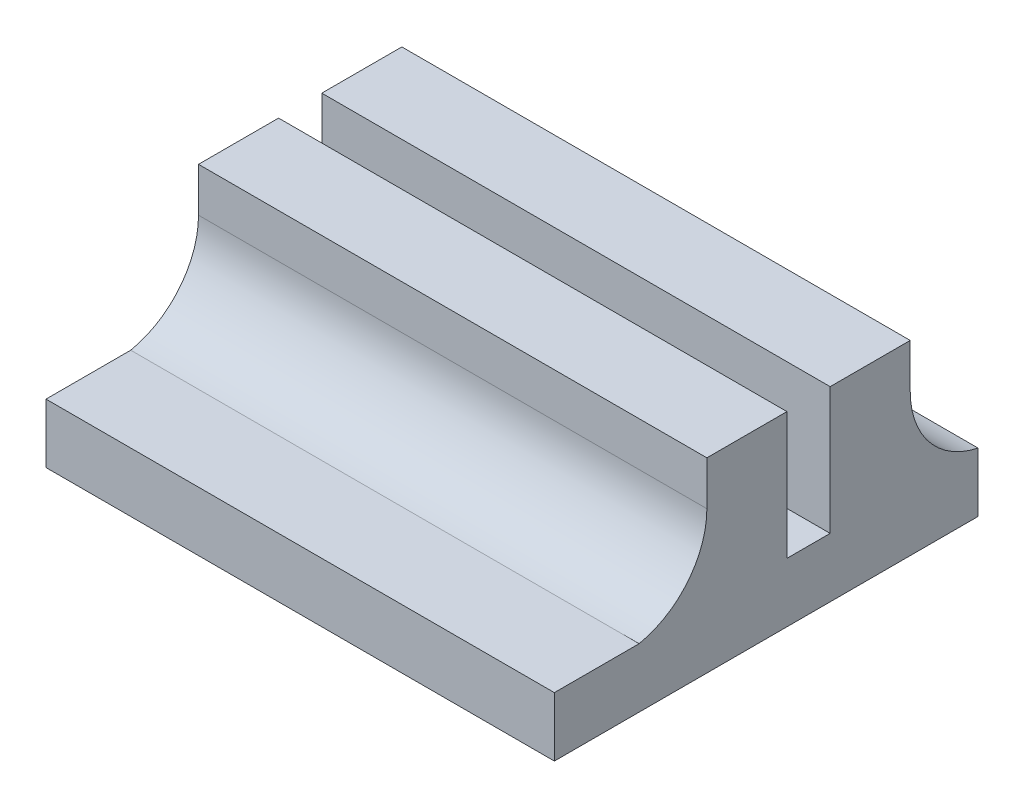
SolidWorks part; units mm, degrees
ref_plane "Front Plane" through (0, 0, 0) normal (0, 0, 1) x (1, 0, 0)
ref_plane "Top Plane" through (0, 0, 0) normal (0, 1, 0) x (1, 0, 0)
ref_plane "Right Plane" through (0, 0, 0) normal (1, 0, 0) x (0, 0, -1)
sketch "Sketch1" plane through (0, 0, 0) normal (0, 1, 0) x (1, 0, 0)
  line L1 (-30, 20) -> (30, 20)
  line L2 (-30, 20) -> (-30, -20)
  line L3 (-30, -20) -> (30, -20)
  line L4 (30, 20) -> (30, -20)
  line L5 (-30, 20) -> (30, -20) construction
  line L6 (-30, -20) -> (30, 20) construction
  point P0 (0, 0)
  dimension "D1" = 60
  dimension "D2" = 40
extrude "Boss-Extrude1" add sketch "Sketch1" along normal blind 22
sketch "Sketch2" plane through (0, 22, 0) normal (0, 1, 0) x (1, 0, 0)
  line L0 (30, -20) -> (30, 20) construction
  line L1 (-30, -2.55) -> (30, -2.55)
  line L2 (-30, -2.55) -> (-30, 2.55)
  line L3 (-30, 2.55) -> (30, 2.55)
  line L4 (30, -2.55) -> (30, 2.55)
  line L5 (-30, -2.55) -> (30, 2.55) construction
  line L6 (-30, 2.55) -> (30, -2.55) construction
  line L7 (-30, 20) -> (-30, -20) construction
  line L8 (-30, 20) -> (30, 20)
  line L9 (-30, 20) -> (-30, 12)
  line L10 (-30, 12) -> (30, 12)
  line L11 (30, 20) -> (30, 12)
  line L12 (30, -20) -> (-30, -20)
  line L13 (30, -20) -> (30, -12)
  line L14 (30, -12) -> (-30, -12)
  line L15 (-30, -20) -> (-30, -12)
  point P0 (0, 0)
  dimension "D1" = 5.1
  dimension "D2" = 8
extrude "Cut-Extrude1" cut sketch "Sketch2" against normal blind 15
fillet "Fillet1" radius 10 2 edges at (0, 7, 12) (0, 7, -12)
sketch "Sketch3" plane through (0, 0, 20) normal (0, 0, 1) x (1, 0, 0)
  line L7 (-30, 7) -> (30, 7)
  line L10 (-30, 7) -> (-30, 0)
  line L11 (-30, 0) -> (30, 0)
  line L12 (30, 7) -> (30, 0)
extrude "Boss-Extrude2" add sketch "Sketch3" along normal blind 10
